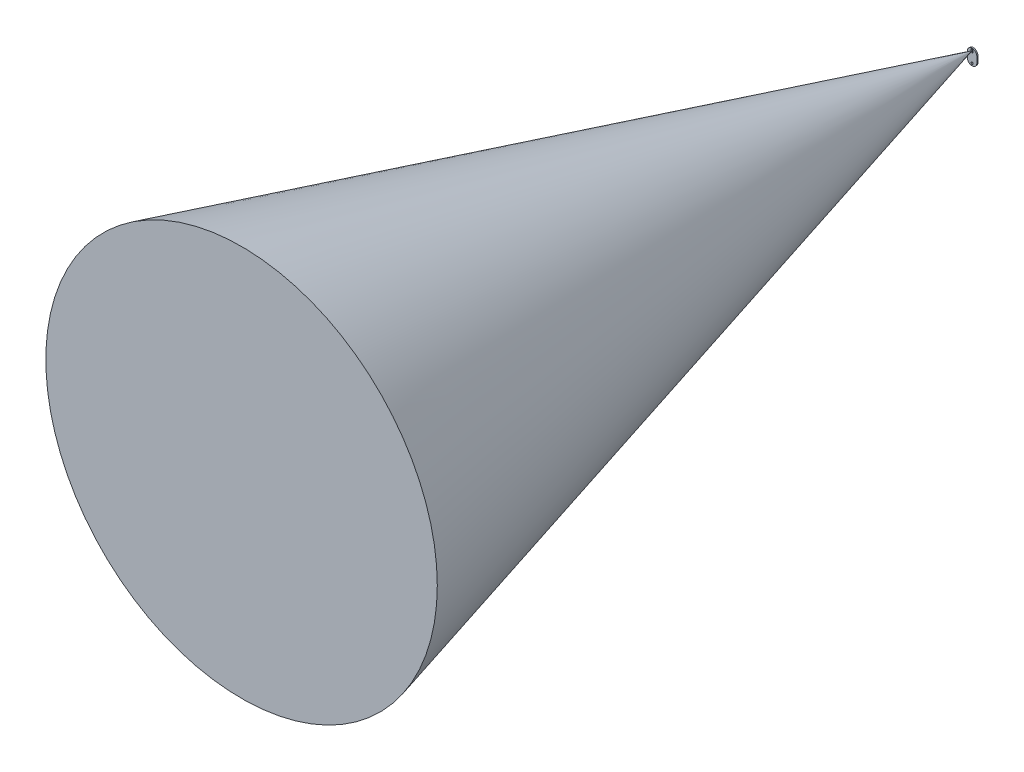
SolidWorks part; units mm, degrees
material "Fibre de verre A"
ref_plane "Plan de face" through (0, 0, 0) normal (0, 0, 1) x (1, 0, 0)
ref_plane "Plan de dessus" through (0, 0, 0) normal (0, 1, 0) x (1, 0, 0)
ref_plane "Plan de droite" through (0, 0, 0) normal (1, 0, 0) x (0, 0, -1)
sketch "Esquisse1" plane through (0, 0, 0) normal (0, 0, 1) x (1, 0, 0)
  line L0 (0, -3.5) -> (0, -11.5) construction
  line L1 (6.5, -3.5) -> (6.5, -11.5)
  line L2 (-6.5, -3.5) -> (-6.5, -11.5)
  arc A0 (6.5, -3.5) -> (-6.5, -3.5) centre (0, -3.5) ccw
  arc A1 (-6.5, -11.5) -> (6.5, -11.5) centre (0, -11.5) ccw
  circle A2 centre (0, -15) radius 1.5
  point P3 (0, -7.5)
  dimension "D2" = 21
  dimension "D4" = 3
  dimension "D1" = 13
  dimension "D3" = 3
  dimension "D5" = 3
extrude "Boss.-Extru.1" add sketch "Esquisse1" along normal blind 1.6
sketch "Esquisse2" plane through (0, 0, 1.6) normal (0, 0, 1) x (1, 0, 0)
  line L0 (-1, 2) -> (1, -2) construction
  line L1 (-1, 2) -> (1, 2)
  line L2 (-1, 2) -> (-1, -2)
  line L3 (-1, -2) -> (1, -2)
  line L4 (1, 2) -> (1, -2)
  dimension "D1" = 2
  dimension "D2" = 4
extrude "Boss.-Extru.2" add sketch "Esquisse2" along normal blind 1
sketch "Esquisse3" plane through (0, 0, 0) normal (1, 0, 0) x (0, 0, -1)
  line L0 (0, 0) -> (-21.7638, 0) construction
  line L1 (-1.6, 0) -> (-1001.6, 0)
  line L2 (-1001.6, 0) -> (-1001.6, 267.9492)
  line L3 (-1001.6, 267.9492) -> (-1.6, 0)
  line L4 (-1.6, -2) -> (-1.6, 2) construction
  dimension "D1" = 1000
  dimension "D2" = 15
revolve "Révolution1" add sketch "Esquisse3" angle 360 about L0
